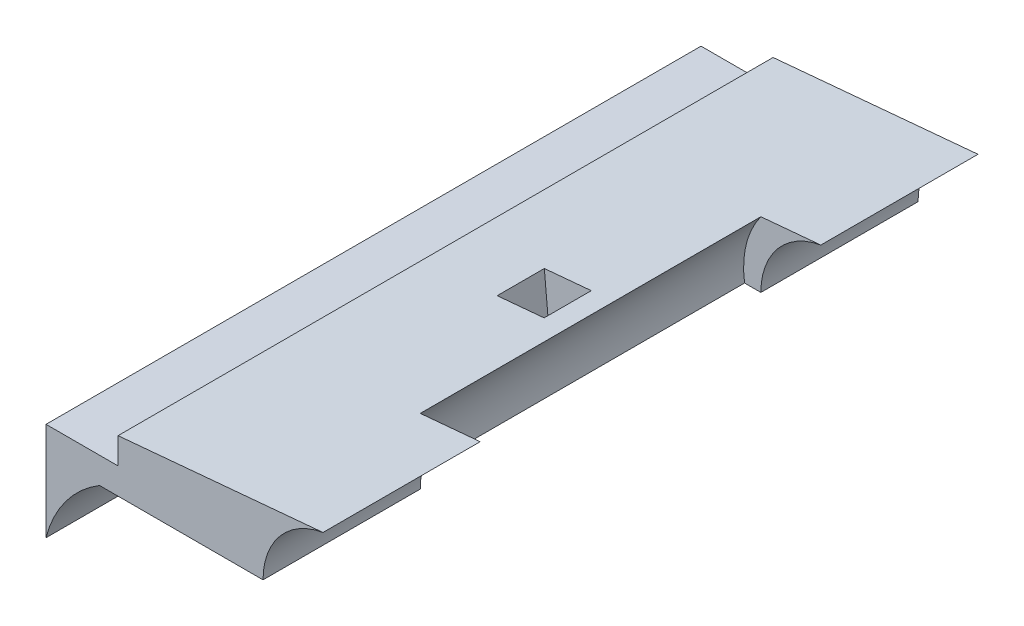
SolidWorks part; units mm, degrees
ref_plane "Alzado" through (0, 0, 0) normal (0, 0, 1) x (1, 0, 0)
ref_plane "Planta" through (0, 0, 0) normal (0, 1, 0) x (1, 0, 0)
ref_plane "Vista lateral" through (0, 0, 0) normal (1, 0, 0) x (0, 0, -1)
sketch "Croquis1" plane through (0, 0, 0) normal (0, 0, 1) x (1, 0, 0)
  line L0 (0, 0) -> (11, 0)
  line L1 (11, 0) -> (11, 4)
  line L3 (0, 0) -> (0, -4)
  line L4 (0, -4) -> (38.3431, -4)
  line L5 (11, 4) -> (44, 7)
  line L6 (44, 7) -> (44, 4)
  circle A0 centre (44, -2) radius 6 construction
  arc A1 (44, 4) -> (38.3431, -4) centre (44, -2) ccw
  dimension "D1" = 12
  dimension "D2" = 33
  dimension "D3" = 4
  dimension "D4" = 11
  dimension "D5" = 4
  dimension "D6" = 3
extrude "Saliente-Extruir1" add sketch "Croquis1" along normal blind 100
ref_plane "Plano1" through (0, 0, 50) normal (0, 0, 1) x (1, 0, 0)
sketch "Croquis3" plane through (0, 0, 50) normal (0, 0, 1) x (1, 0, 0)
  arc A0 (44, 4) -> (38.3431, -4) centre (44, -2) ccw construction
  arc A1 (44, 4) -> (38.3431, -4) centre (44, -2) ccw construction
  circle A2 centre (44, -2) radius 13.5
  dimension "D1" = 27
extrude "Cortar-Extruir2" cut sketch "Croquis3" against normal blind 26 and the other way blind 26
sketch "Croquis11" plane through (-0.2705, 2.9754, 0) normal (-0.0905, 0.9959, 0) x (0.9959, 0.0905, 0)
  line L0 (33.543, -24) -> (33.543, -76) construction
  line L1 (33.543, -50) -> (31.543, -50) construction
  line L3 (22.843, -46.4) -> (30.043, -46.4)
  line L4 (22.843, -46.4) -> (22.843, -53.6)
  line L5 (22.843, -53.6) -> (30.043, -53.6)
  line L6 (30.043, -46.4) -> (30.043, -53.6)
  line L7 (22.843, -46.4) -> (30.043, -53.6) construction
  line L8 (22.843, -53.6) -> (30.043, -46.4) construction
  point P6 (26.443, -50)
  dimension "D1" = 7.2
  dimension "D2" = 7.2
  dimension "D3" = 7
  dimension "D4" = 0
extrude "Cortar-Extruir6" cut sketch "Croquis11" against normal blind 6
sketch "Croquis12" plane through (0.2727, -2.9999, 0) normal (-0.0905, 0.9959, 0) x (0.9959, 0.0905, 0)
  line L0 (22.843, -46.4) -> (30.043, -53.6) construction
  line L2 (23.693, -52.75) -> (29.193, -52.75)
  line L3 (23.693, -52.75) -> (23.693, -47.25)
  line L4 (23.693, -47.25) -> (29.193, -47.25)
  line L5 (29.193, -52.75) -> (29.193, -47.25)
  line L6 (23.693, -52.75) -> (29.193, -47.25) construction
  line L7 (23.693, -47.25) -> (29.193, -52.75) construction
  point P4 (26.443, -50)
  dimension "D1" = 5.5
extrude "Cortar-Extruir7" cut sketch "Croquis12" against normal blind 6
sketch "Croquis13" plane through (-0.2705, 2.9754, 0) normal (-0.0905, 0.9959, 0) x (0.9959, 0.0905, 0)
  line L0 (33.543, -76) -> (33.543, -100) construction
  line L1 (44.4531, -100) -> (11.317, -100) construction
sketch "Croquis14" plane through (0, 0, 100) normal (0, 0, 1) x (1, 0, 0)
  line L0 (33.1347, 6.0122) -> (33.1347, -4) construction
  line L1 (0, -4) -> (38.3431, -4) construction
  arc A0 (33.1347, -4) -> (44, 7) centre (44.1356, -4) cw
extrude "Cortar-Extruir11" cut sketch "Croquis14" against normal through all and the other way through all flip side to cut
sketch "Croquis15" plane through (0, 0, 100) normal (0, 0, 1) x (1, 0, 0)
  line L0 (0, -4) -> (0, -15)
  line L1 (0, -4) -> (33.1347, -4) construction
  line L8 (42.2853, 6.8441) -> (11, 4)
  line L9 (11, 4) -> (11, 0)
  line L10 (11, 0) -> (0, 0)
  line L11 (0, 0) -> (0, -4)
  line L12 (0, -4) -> (33.1347, -4)
  line L17 (0, -4) -> (8.1699, -4)
  arc A0 (0, -15) -> (8.1699, -4) centre (17.5016, -19.4647) cw
  arc A2 (42.2853, 6.8441) -> (33.1347, -4) centre (44.1356, -4) ccw
  point P6 (8.1699, -4)
  dimension "D1" = 11
  dimension "D2" = 0
extrude "Saliente-Extruir2" add sketch "Croquis15" against normal up to surface (100 mm away) up to face at (15.9063, 0.7528, 0)
